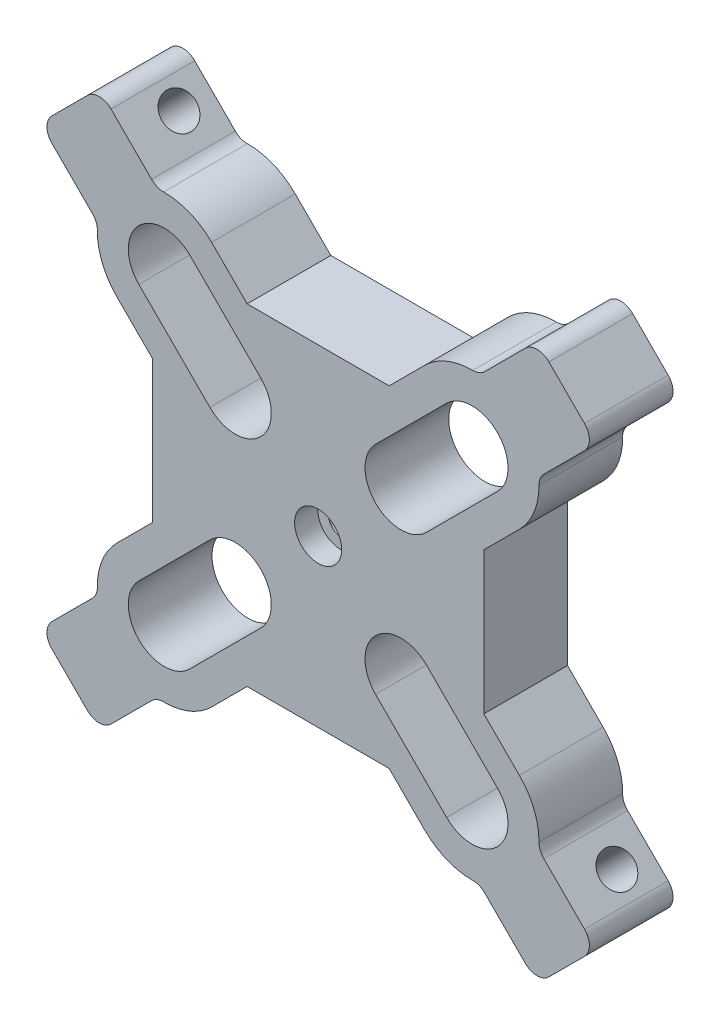
SolidWorks part; units mm, degrees
ref_plane "정면" through (0, 0, 0) normal (0, 0, 1) x (1, 0, 0)
ref_plane "윗면" through (0, 0, 0) normal (0, 1, 0) x (1, 0, 0)
ref_plane "우측면" through (0, 0, 0) normal (1, 0, 0) x (0, 0, -1)
sketch "Sketch1" plane through (0, 0, 0) normal (0, 0, 1) x (1, 0, 0)
  line L1 (0, 0) -> (-71.12, 0)
  line L2 (0, 0) -> (0, 71.12)
  line L3 (0, 71.12) -> (-71.12, 71.12)
  line L4 (-71.12, 0) -> (-71.12, 71.12)
  dimension "D1" = 71.12
  dimension "D2" = 71.12
extrude "Extrude1" add sketch "Sketch1" along normal blind 12.7
sketch "Sketch3" plane through (0, 0, 12.7) normal (0, 0, 1) x (1, 0, 0)
  line L0 (-71.12, 71.12) -> (0, 0)
  line L1 (0, 71.12) -> (-71.12, 0)
  line L2 (-58.9087, 58.9087) -> (-56.8432, 60.9741)
  line L3 (-56.8432, 60.9741) -> (-46.0669, 50.1978)
  line L4 (-46.0669, 50.1978) -> (-50.1978, 46.0669)
  line L5 (-50.1978, 46.0669) -> (-60.9741, 56.8432)
  line L6 (-60.9741, 56.8432) -> (-58.9087, 58.9087)
  circle A0 centre (-58.9087, 58.9087) radius 2.921
  circle A1 centre (-48.1324, 48.1324) radius 2.921
  dimension "D2" = 5.842
  dimension "D1" = 17.78
  dimension "D4" = 15.24
extrude "Cut-Extrude1" cut sketch "Sketch3" against normal through all contours A0 | L3 L4 L5 L6 L2 | A1
ref_plane "Plane1" through (-35.56, 0, 0) normal (1, 0, 0) x (0, 0, -1)
ref_plane "Plane2" through (0, 35.56, 0) normal (0, 1, 0) x (-1, 0, 0)
mirror "Mirror1" about plane through (0, 35.56, 0) normal (0, 1, 0) of "Cut-Extrude1"
mirror "Mirror2" about plane through (-35.56, 0, 0) normal (1, 0, 0) of "Cut-Extrude1"
mirror "Mirror3" about plane through (0, 35.56, 0) normal (0, 1, 0) of "Mirror2"
sketch "Sketch6" plane through (0, 0, 12.7) normal (0, 0, 1) x (1, 0, 0)
  line L0 (-58.9087, 58.9087) -> (-55.0472, 62.7702)
  line L1 (-55.0472, 62.7702) -> (-44.2708, 51.9939)
  line L2 (-44.2708, 51.9939) -> (-48.1324, 48.1324)
  line L3 (-48.1324, 48.1324) -> (-51.9939, 44.2708)
  line L4 (-51.9939, 44.2708) -> (-62.7702, 55.0472)
  line L5 (-62.7702, 55.0472) -> (-58.9087, 58.9087)
  circle A0 centre (-58.9087, 58.9087) radius 5.461
  circle A1 centre (-48.1324, 48.1324) radius 5.461
  dimension "D2" = 10.922
  dimension "D3" = 15.24
extrude "Cut-Extrude3" cut sketch "Sketch6" against normal through all contours A0 | A1 | L4 L5 L0 L1 L2 L3
mirror "Mirror4" about plane through (-35.56, 0, 0) normal (1, 0, 0) of "Cut-Extrude3"
mirror "Mirror5" about plane through (0, 35.56, 0) normal (0, 1, 0) of "Cut-Extrude3"
mirror "Mirror6" about plane through (-35.56, 0, 0) normal (1, 0, 0) of "Mirror5"
sketch "Sketch7" plane through (0, 0, 12.7) normal (0, 0, 1) x (1, 0, 0)
  line L0 (-5.0271, 19.3955) -> (-15.8034, 30.1718)
  line L1 (0, 35.56) -> (-71.12, 35.56) construction
  line L2 (0, 0) -> (0, 71.12) construction
  line L3 (-19.3955, 5.0271) -> (-30.1718, 15.8034)
  line L4 (-71.12, 71.12) -> (-71.12, 0) construction
  line L7 (-35.56, 0) -> (-35.56, 71.12) construction
  line L8 (-71.12, 0) -> (0, 0) construction
  line L10 (0, 71.12) -> (-71.12, 71.12) construction
  line L11 (-51.7245, 5.0271) -> (-40.9482, 15.8034)
  line L12 (-66.0929, 19.3955) -> (-55.3166, 30.1718)
  line L13 (-66.0929, 51.7245) -> (-55.3166, 40.9482)
  line L14 (-51.7245, 66.0929) -> (-40.9482, 55.3166)
  line L15 (-19.3955, 66.0929) -> (-30.1718, 55.3166)
  line L16 (-5.0271, 51.7245) -> (-15.8034, 40.9482)
  line L17 (-10.4153, 46.3363) -> (-10.4153, 24.7837)
  line L18 (-24.7837, 10.4153) -> (-46.3363, 10.4153)
  line L19 (-24.7837, 60.7047) -> (-46.3363, 60.7047)
  line L20 (-60.7047, 46.3363) -> (-60.7047, 24.7837)
  circle A0 centre (-12.2113, 12.2113) radius 10.16
  circle A1 centre (-22.9876, 22.9876) radius 10.16
  circle A2 centre (-58.9087, 12.2113) radius 10.16
  circle A3 centre (-48.1324, 22.9876) radius 10.16
  circle A4 centre (-58.9087, 58.9087) radius 10.16
  circle A5 centre (-48.1324, 48.1324) radius 10.16
  circle A6 centre (-12.2113, 58.9087) radius 10.16
  circle A7 centre (-22.9876, 48.1324) radius 10.16
  line M5 (0, 0) -> (0, 71.12)
  line M6 (0, 71.12) -> (-71.12, 71.12)
  line M7 (-71.12, 71.12) -> (-71.12, 0)
  line M8 (-71.12, 0) -> (0, 0)
  dimension "D1" = 20.32
extrude "Cut-Extrude5" cut sketch "Sketch7" against normal through all contours A0 M8 M5 M6 M7 region at (-35.56, 1.0058, 12.7)
sketch "Sketch10" plane through (0, 0, 12.7) normal (0, 0, 1) x (1, 0, 0)
  line L0 (-58.9087, 58.9087) -> (-73.2771, 73.2771)
  line L1 (-73.2771, 73.2771) -> (-77.7672, 68.7869)
  line L2 (-77.7672, 68.7869) -> (-68.7869, 59.8067)
  line L3 (-51.7245, 66.0929) -> (-66.0929, 51.7245)
  line L4 (-68.7869, 59.8067) -> (-59.8067, 68.7869)
  line L5 (-59.8067, 68.7869) -> (-68.7869, 77.7672)
  line L6 (-68.7869, 77.7672) -> (-73.2771, 73.2771)
  arc M21 (-19.3955, 5.0271) -> (-5.0271, 19.3955) centre (-12.2113, 12.2113) ccw
  dimension "D4" = 12.7
  dimension "D1" = 6.35
  dimension "D2" = 6.35
  dimension "D3" = 20.32
extrude "Extrude2" add sketch "Sketch10" against normal blind 12.7 contours M21 | M21 | L1 L2 L4 L5 L6
hole_wizard "CBORE for #6 Socket Head Cap Screw1" positions "3DSketch1" profile "Sketch11" counterbore size "#6" standard "Ansi Inch" end condition through all
sketch3d "3DSketch1"
  line L6 (-24.7837, 60.7047, 12.7) -> (-46.3363, 60.7047, 12.7) construction
  line L9 (-10.4153, 46.3363, 12.7) -> (-10.4153, 24.7837, 12.7) construction
  point P0 (-35.5613, 35.5587, 12.7)
  dimension "D1" = 25.146
  dimension "D2" = 25.146
sketch "Sketch11" plane through (-35.5613, 35.5587, 12.7) normal (1, 0, 0) x (0, -1, 0)
  line L0 (0, 0) -> (0, 12.7)
  line L1 (0, 12.7) -> (1.8986, 12.7)
  line L3 (1.8986, 12.7) -> (1.8986, 3.5052)
  line L4 (1.8986, 3.5052) -> (3.5725, 3.5052)
  line L5 (3.5725, 3.5052) -> (3.5725, 0)
  line L7 (3.5725, 0) -> (0, 0)
  line L11 (0, -6.35) -> (0, 107.95) construction
  dimension "Thru Hole Dia." = 3.7973
  dimension "Thru Hole Depth" = 12.7
  dimension "C'Bore Dia." = 7.145
  dimension "C'Bore Depth" = 3.5052
hole_wizard "#6 (0.204) Diameter Hole1" positions "3DSketch2" profile "Sketch15" hole size "#6" standard "Ansi Inch"
sketch3d "3DSketch2"
  line L0 (-68.7869, 77.7672, 0) -> (-68.7869, 77.7672, 12.7) construction
  line L1 (-60.0267, 69.007, 0) -> (-68.7869, 77.7672, 0) construction
  point P0 (-64.2968, 73.2771, 5.08)
  dimension "D1" = 6.35
  dimension "D2" = 5.08
sketch "Sketch15" plane through (-64.2968, 73.2771, 5.08) normal (0, 0, 1) x (-0.7071, 0.7071, 0)
  line L0 (0, 0) -> (0, 67.5967)
  line L1 (0, 67.5967) -> (2.5908, 66.04)
  line L2 (2.5908, 66.04) -> (2.5908, 0)
  line L5 (2.5908, 0) -> (0, 0)
  line L10 (0, 67.5967) -> (-2.5908, 66.04) construction
  line L11 (0, -6.35) -> (0, 107.95) construction
  dimension "Hole Dia." = 5.1816
  dimension "Hole Depth" = 66.04
  dimension "Drill Angle" = 118
mirror "Mirror8" about plane through (0, 35.56, 0) normal (0, 1, 0) of "#6 (0.204) Diameter Hole1", "Extrude2"
mirror "Mirror9" about plane through (-35.56, 0, 0) normal (1, 0, 0) of "Mirror8", "Extrude2", "#6 (0.204) Diameter Hole1"
fillet "Fillet3" radius 2.54 16 edges at (-2.113, 11.0933, 6.35) (-11.0933, 2.113, 6.35) (-60.0267, 2.113, 6.35) (-69.007, 11.0933, 6.35) (-69.007, 60.0267, 6.35) (-60.0267, 69.007, 6.35) (-11.0933, 69.007, 6.35) (-2.113, 60.0267, 6.35) (6.6472, 2.3331, 6.35) (-2.3331, -6.6472, 6.35) (-68.7869, -6.6472, 6.35) (-77.7672, 2.3331, 6.35) (-77.7672, 68.7869, 6.35) (-68.7869, 77.7672, 6.35) (-2.3331, 77.7672, 6.35) (6.6472, 68.7869, 6.35)
